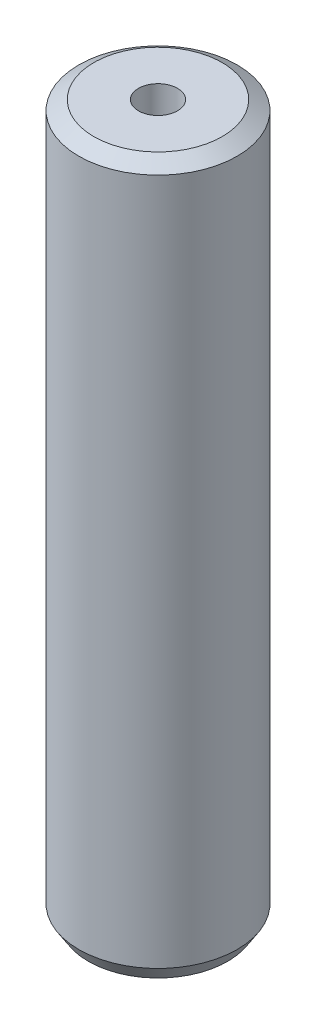
SolidWorks part; units mm, degrees
ref_plane "Front Plane" through (0, 0, 0) normal (0, 0, 1) x (1, 0, 0)
ref_plane "Top Plane" through (0, 0, 0) normal (0, 1, 0) x (1, 0, 0)
ref_plane "Right Plane" through (0, 0, 0) normal (1, 0, 0) x (0, 0, -1)
sketch "Sketch1" plane through (0, 0, 0) normal (0, 1, 0) x (1, 0, 0)
  circle A0 centre (0, 0) radius 7.5
  dimension "SHAFT_OD" = 15
extrude "Boss-Extrude1" add sketch "Sketch1" along normal blind 67.4
sketch "Sketch2" plane through (0, 0, 0) normal (0, 1, 0) x (1, 0, 0)
  circle A0 centre (0, 0) radius 1.8496
  dimension "BORE_D" = 3.6992
extrude "Cut-Extrude1" cut sketch "Sketch2" along normal through all
chamfer "Chamfer1" distance 0.8974 angle 57.719 2 edges at (0, 67.4, 7.5) (0, 0, 7.5) first distance on face at (0, 67.4, 7.5) first distance on face at (0, 0, 1.8496)
